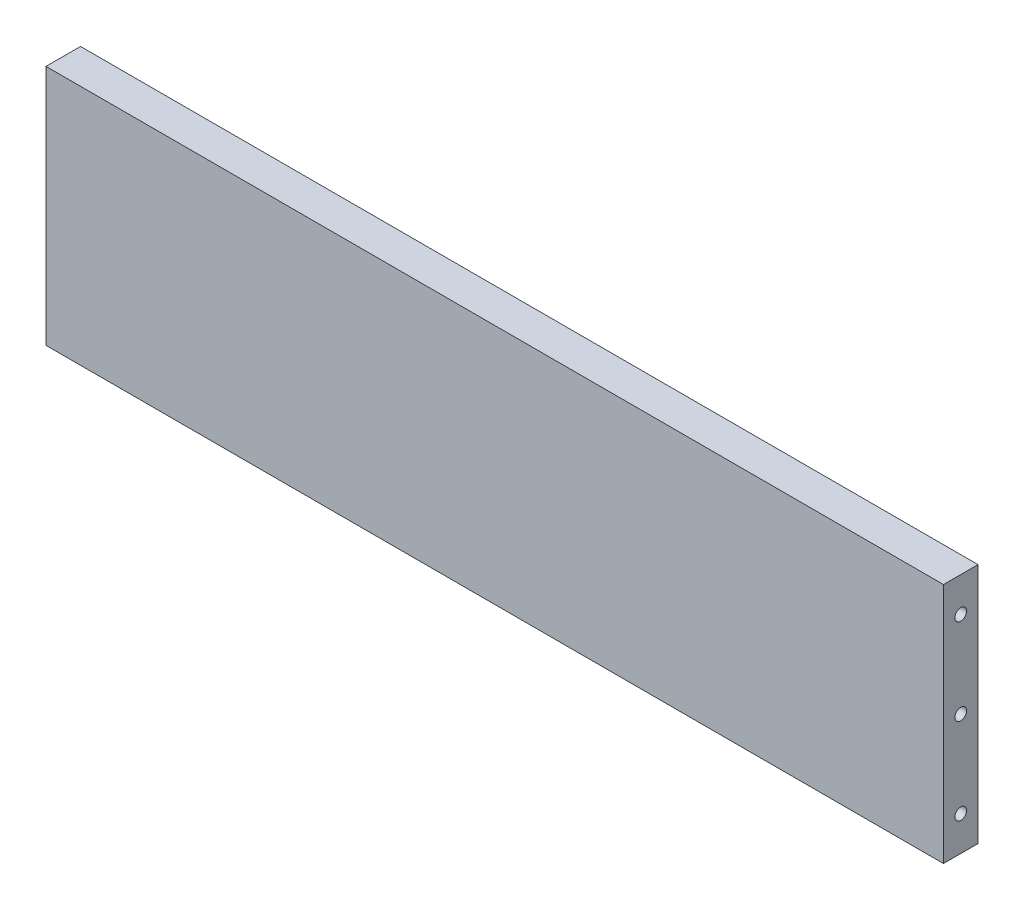
SolidWorks part; units mm, degrees
ref_plane "Front Plane" through (0, 0, 0) normal (0, 0, 1) x (1, 0, 0)
ref_plane "Top Plane" through (0, 0, 0) normal (0, 1, 0) x (1, 0, 0)
ref_plane "Right Plane" through (0, 0, 0) normal (1, 0, 0) x (0, 0, -1)
sketch "Sketch1" plane through (0, 0, 0) normal (0, 0, 1) x (1, 0, 0)
  line L1 (0, 0) -> (330.2, 0)
  line L2 (0, 0) -> (0, 88.9)
  line L3 (0, 88.9) -> (330.2, 88.9)
  line L4 (330.2, 0) -> (330.2, 88.9)
  dimension "D1" = 88.9
  dimension "D2" = 330.2
extrude "Boss-Extrude1" add sketch "Sketch1" along normal blind 12.7
sketch "Sketch3" plane through (0, 0, 0) normal (-1, 0, 0) x (0, 0, 1)
  line L0 (0, 88.9) -> (0, 0) construction
  line L1 (12.7, 88.9) -> (0, 88.9) construction
  line L2 (12.7, 0) -> (0, 0) construction
  circle A0 centre (6.35, 76.2) radius 2.1463
  circle A1 centre (6.35, 12.7) radius 2.1463
  circle A2 centre (6.35, 44.45) radius 2.1463
  dimension "D7" = 4.2926
  dimension "D8" = 4.2926
  dimension "D9" = 4.2926
  dimension "D1" = 6.35
  dimension "D2" = 12.7
  dimension "D3" = 12.7
  dimension "D4" = 6.35
  dimension "D5" = 6.35
  dimension "D6" = 44.45
extrude "Cut-Extrude1" cut sketch "Sketch3" against normal blind 38.1
sketch "Sketch5" plane through (330.2, 0, 0) normal (1, 0, 0) x (0, 0, -1)
  line L0 (0, 0) -> (0, 88.9) construction
  line L1 (-12.7, 88.9) -> (0, 88.9) construction
  line L2 (-12.7, 0) -> (0, 0) construction
  circle A0 centre (-6.35, 76.2) radius 2.1463
  circle A1 centre (-6.35, 12.7) radius 2.1463
  circle A2 centre (-6.35, 44.45) radius 2.1463
  dimension "D7" = 4.2926
  dimension "D8" = 4.2926
  dimension "D9" = 4.2926
  dimension "D1" = 6.35
  dimension "D2" = 6.35
  dimension "D3" = 6.35
  dimension "D4" = 12.7
  dimension "D5" = 12.7
  dimension "D6" = 44.45
extrude "Cut-Extrude2" cut sketch "Sketch5" against normal blind 38.1
